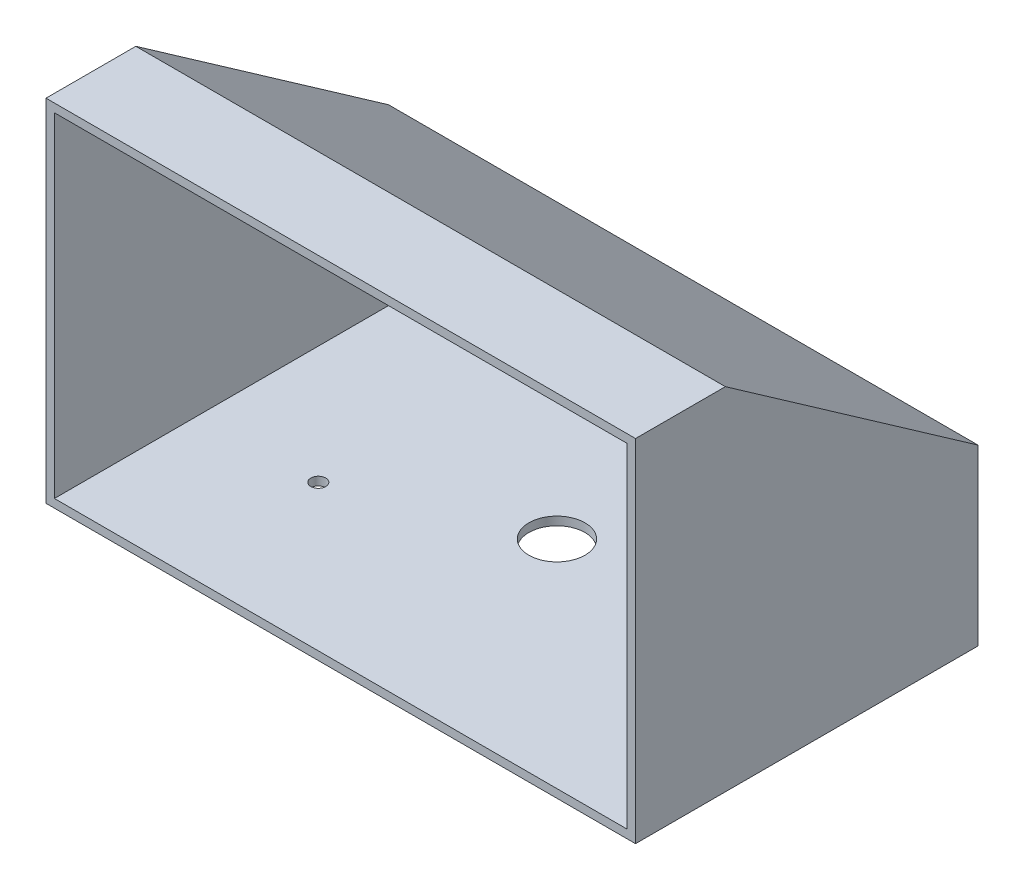
SolidWorks part; units mm, degrees
ref_plane "Front Plane" through (0, 0, 0) normal (0, 0, 1) x (1, 0, 0)
ref_plane "Top Plane" through (0, 0, 0) normal (0, 1, 0) x (1, 0, 0)
ref_plane "Right Plane" through (0, 0, 0) normal (1, 0, 0) x (0, 0, -1)
ref_plane "PL_Ym105" through (-105, 0, 0) normal (1, 0, 0) x (0, 0, -1)
sketch "SK_Body" plane through (-105, 0, 0) normal (1, 0, 0) x (0, 0, -1)
  line L0 (70, 0) -> (-52, 0)
  line L1 (-52, 0) -> (-52, 125)
  line L2 (-52, 125) -> (-20, 125)
  line L3 (-20, 125) -> (70, 61.9813)
  line L4 (70, 61.9813) -> (70, 0)
  dimension "D1" = 70
  dimension "D2" = 52
  dimension "D3" = 52
  dimension "D4" = 125
  dimension "D5" = 20
  dimension "D6" = 125
  dimension "D7" = 70
  dimension "D8" = 61.9813
extrude "EX_Body" add sketch "SK_Body" along normal blind 210
shell "Shell" thickness 3 removed face at (0, 62.5, 52)
sketch "SK_FloorHoles" plane through (0, 0, 0) normal (0, 1, 0) x (1, 0, 0)
  circle A0 centre (60, 0) radius 2.65
  circle A1 centre (-60, 0) radius 2.65
  circle A2 centre (0, 25) radius 10
  dimension "D2" = 5.3
  dimension "D4" = 5.3
  dimension "D6" = 20
  dimension "D1" = 60
  dimension "D3" = 60
  dimension "D5" = 25
extrude "CUT_FloorHoles" cut sketch "SK_FloorHoles" along normal blind 3
ref_axis "AX_X" through (0, 0, -76.1) along (0, 0, 1)
ref_axis "AX_Y" through (115.5, 0, 0) along (-1, 0, 0)
ref_axis "AX_Z" through (0, 131.25, 0) along (0, -1, 0)
sketch "SK_F_IF_Bezel" plane through (0, 0, 0) normal (0, 1, 0) x (1, 0, 0)
  point P0 (0, -52)
  dimension "D1" = 52
ref_plane "PL_Zp3" through (0, 3, 0) normal (0, 1, 0) x (1, 0, 0)
sketch "SK_F_IF_YAdapter" plane through (0, 3, 0) normal (0, 1, 0) x (1, 0, 0)
  point P0 (0, 40)
  dimension "D1" = 40
sketch "SK_F_IF_Display" plane through (0, 0, 0) normal (1, 0, 0) x (0, 0, -1)
  line L0 (70, 61.9813) -> (-20, 125) construction
  point P3 (25, 93.4907)
  dimension "D1" = 70
  dimension "D2" = 61.9813
  dimension "D3" = 20
  dimension "D4" = 125
